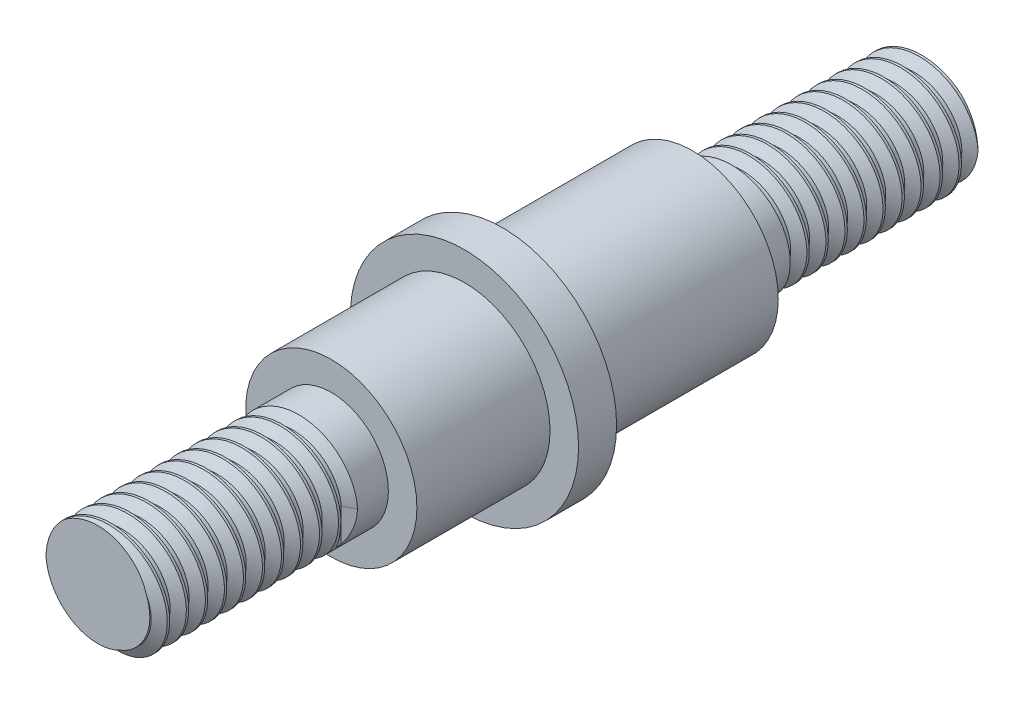
SolidWorks part; units mm, degrees
material "AISI 1020"
ref_plane "Plano frontal" through (0, 0, 0) normal (0, 0, 1) x (1, 0, 0)
ref_plane "Plano superior" through (0, 0, 0) normal (0, 1, 0) x (1, 0, 0)
ref_plane "Plano direito" through (0, 0, 0) normal (1, 0, 0) x (0, 0, -1)
sketch "Esboço1" plane through (0, 0, 0) normal (0, 0, 1) x (1, 0, 0)
  circle A0 centre (0, 0) radius 3
  dimension "D1" = 6
extrude "Ressalto-extrusão1" add sketch "Esboço1" along normal blind 12
sketch "Esboço2" plane through (0, 0, 12) normal (0, 0, 1) x (1, 0, 0)
  circle A0 centre (0, 0) radius 4.5
  dimension "D1" = 9
extrude "Ressalto-extrusão2" add sketch "Esboço2" along normal blind 10
sketch "Esboço3" plane through (0, 0, 22) normal (0, 0, 1) x (1, 0, 0)
  circle A0 centre (0, 0) radius 6
  dimension "D1" = 12
extrude "Ressalto-extrusão3" add sketch "Esboço3" along normal blind 2
sketch "Esboço4" plane through (0, 0, 24) normal (0, 0, 1) x (1, 0, 0)
  circle A0 centre (0, 0) radius 4.5
  dimension "D1" = 9
extrude "Ressalto-extrusão4" add sketch "Esboço4" along normal blind 7
sketch "Esboço5" plane through (0, 0, 31) normal (0, 0, 1) x (1, 0, 0)
  circle A0 centre (0, 0) radius 3
  dimension "D1" = 6
extrude "Ressalto-extrusão5" add sketch "Esboço5" along normal blind 12
thread "Rosca1" pitch 1 method cut profile "Perfil da rosca1" start angle 0, offset 1, length 10.5, pitch 1, diameter 6
ref_plane "Plano1" through (3, 0, -1) normal (0, -1, 0) x (1, 0, 0)
sketch "Perfil da rosca1" plane through (3, 0, -1) normal (0, -1, 0) x (1, 0, 0)
  line L0 (0, 0) -> (0, 1) construction
  line L11 (0, 0) -> (0, 0.875)
  line L12 (0, 0.875) -> (-0.5413, 0.5625)
  line L13 (-0.5413, 0.5625) -> (-0.5413, 0.3125)
  line L15 (-0.5413, 0.3125) -> (0, 0)
  line L17 (-0.5413, 0.4375) -> (0, 0.4375) construction
  point P2 (0, 0)
  dimension "Pitch" = 1
  dimension "Profile_Angle" = 60
  dimension "Profile_Land" = 0.25
  dimension "Profile_Height" = 0.5413
sketch "Esboço7" plane through (0, 0, 0) normal (0, 1, 0) x (1, 0, 0)
  line L4 (-2.4587, -9.8125) -> (-3, -9.5)
  line L5 (-3, -9.5) -> (-3, -10.375)
  line L6 (-3, -10.375) -> (-2.4587, -10.0625)
  line L7 (-2.4587, -10.0625) -> (-2.4587, -9.8125)
  line L8 (-2.4587, -9.8125) -> (-3, -9.5)
  line L9 (-3, -9.5) -> (-3, -10.375)
  line L10 (-3, -10.375) -> (-2.4587, -10.0625)
  line L11 (-2.4587, -10.0625) -> (-2.4587, -9.8125)
  dimension "D1" = 0
extrude "Corte-extrusão2" cut sketch "Esboço7" against normal blind 10
thread "Rosca2" pitch 1 method cut profile "Perfil da rosca2" start angle 0, offset 1, length 10.5, pitch 1, diameter 6
ref_plane "Plano2" through (-3, 0, 44) normal (0, -1, 0) x (-1, 0, 0)
sketch "Perfil da rosca2" plane through (-3, 0, 44) normal (0, -1, 0) x (-1, 0, 0)
  line L0 (0, 0) -> (0, 1) construction
  line L11 (0, 0) -> (0, 0.875)
  line L12 (0, 0.875) -> (-0.5413, 0.5625)
  line L13 (-0.5413, 0.5625) -> (-0.5413, 0.3125)
  line L15 (-0.5413, 0.3125) -> (0, 0)
  line L17 (-0.5413, 0.4375) -> (0, 0.4375) construction
  point P2 (0, 0)
  dimension "Pitch" = 1
  dimension "Profile_Angle" = 60
  dimension "Profile_Land" = 0.25
  dimension "Profile_Height" = 0.5413
sketch "Esboço10" plane through (0, 0, 0) normal (0, 1, 0) x (1, 0, 0)
  line L4 (2.4587, -33.1875) -> (3, -33.5)
  line L5 (3, -33.5) -> (3, -32.625)
  line L6 (3, -32.625) -> (2.4587, -32.9375)
  line L7 (2.4587, -32.9375) -> (2.4587, -33.1875)
  line L8 (2.4587, -33.1875) -> (3, -33.5)
  line L9 (3, -33.5) -> (3, -32.625)
  line L10 (3, -32.625) -> (2.4587, -32.9375)
  line L11 (2.4587, -32.9375) -> (2.4587, -33.1875)
  dimension "D1" = 0
extrude "Corte-extrusão3" cut sketch "Esboço10" against normal blind 10
